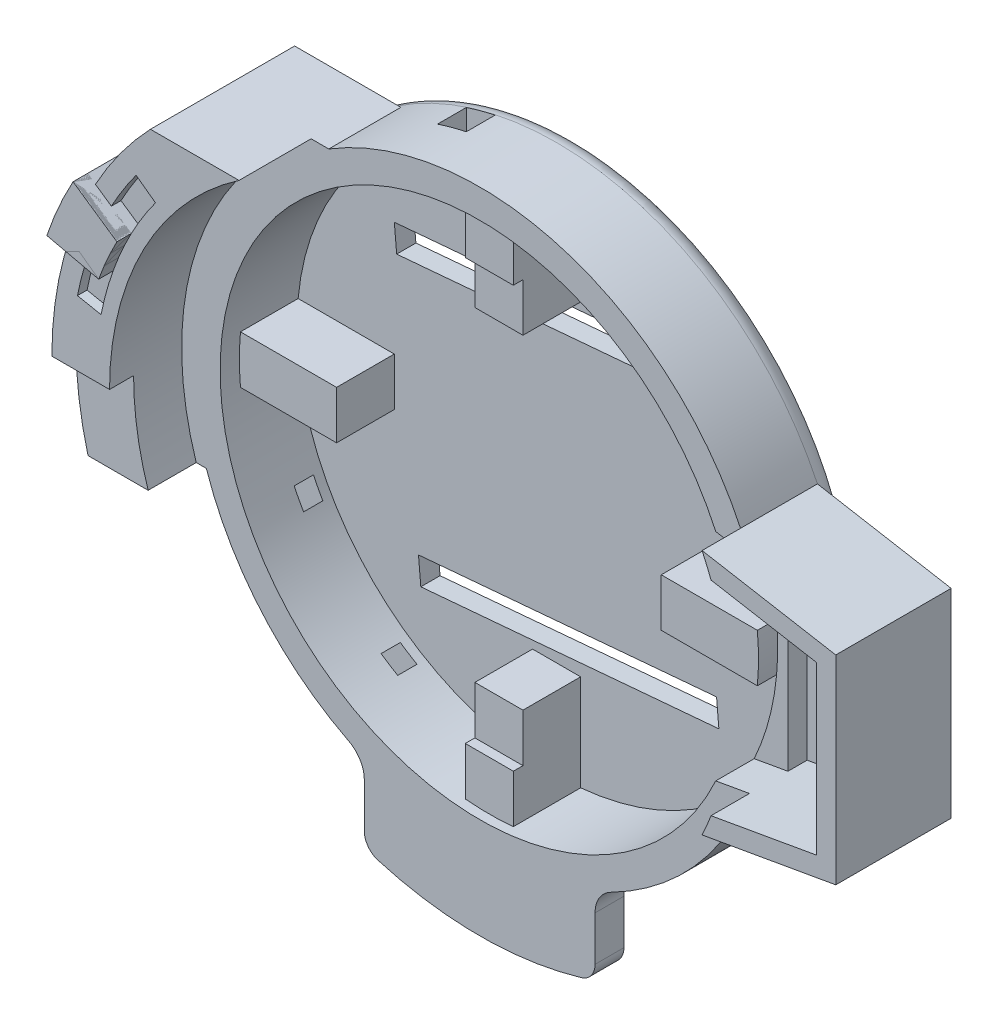
SolidWorks part; units mm, degrees
material "AISI 304"
ref_plane "Front Plane" through (0, 0, 0) normal (0, 0, 1) x (1, 0, 0)
ref_plane "Top Plane" through (0, 0, 0) normal (0, 1, 0) x (1, 0, 0)
ref_plane "Right Plane" through (0, 0, 0) normal (1, 0, 0) x (0, 0, -1)
sketch "草图1" plane through (0, 0, 0) normal (0, 0, 1) x (1, 0, 0)
  circle A0 centre (0, 0) radius 30
  dimension "D1" = 60
extrude "凸台-拉伸1" add sketch "草图1" along normal blind 2
sketch "草图5" plane through (0, 0, 2) normal (0, 0, 1) x (1, 0, 0)
  circle A0 centre (0, 0) radius 30
  circle A1 centre (0, 0) radius 27
  dimension "D1" = 60
  dimension "D2" = 54
extrude "凸台-拉伸2" add sketch "草图5" along normal blind 10 contours A0 | A1
sketch "草图6" plane through (0, 0, 12) normal (0, 0, 1) x (1, 0, 0)
  line L0 (-12, -27.4955) -> (-12, -35.4955)
  line L2 (12, -35.4955) -> (12, -27.4955)
  circle A0 centre (0, 0) radius 30 construction
  arc A1 (-12, -27.4955) -> (12, -27.4955) centre (0, 0) ccw
  arc A2 (-12, -35.4955) -> (12, -35.4955) centre (0, 0) ccw
  dimension "D1" = 8
  dimension "D2" = 24
extrude "凸台-拉伸3" add sketch "草图6" against normal blind 3
fillet "圆角2" radius 3 1 edges at (-12, -27.4955, 10.5)
fillet "圆角3" radius 3 1 edges at (12, -27.4955, 10.5)
sketch "草图8" plane through (0, 0, 12) normal (0, 0, 1) x (1, 0, 0)
  line L0 (27.037, -13) -> (41.037, -13)
  line L1 (41.037, -13) -> (41.037, 13)
  line L2 (41.037, 13) -> (27.037, 13)
  circle A0 centre (0, 0) radius 30 construction
  arc A1 (27.037, -13) -> (27.037, 13) centre (0, 0) ccw
extrude "凸台-拉伸4" add sketch "草图8" against normal blind 6
sketch "草图13" plane through (0, 0, 12) normal (0, 0, 1) x (1, 0, 0)
  line L0 (-26.7466, 25.566) -> (-15.6965, 25.566)
  line L1 (-37, 0) -> (-30, 0)
  arc A0 (-26.7466, 25.566) -> (-37, 0) centre (0, 0) ccw
  arc A1 (-15.6965, 25.566) -> (-30, 0) centre (0, 0) ccw
  dimension "D1" = 37
  dimension "D2" = 30
extrude "凸台-拉伸6" add sketch "草图13" against normal mid plane 15
sketch "草图14" plane through (0, 0, 19.5) normal (0, 0, 1) x (1, 0, 0)
  circle A0 centre (0, 0) radius 31
  dimension "D1" = 62
extrude "切除-拉伸3" cut sketch "草图14" against normal up to surface (7.5 mm away) up to face at (7.2727, -12.6009, 12)
chamfer "倒角4" distance 15 angle 10 1 edges at (41.037, 13, 9) first distance on face at (34.037, 13, 9)
chamfer "倒角5" distance 15 angle 10 1 edges at (41.037, -13, 9) first distance on face at (34.037, -13, 9)
sketch "草图16" plane through (0, 0, 12) normal (0, 0, 1) x (1, 0, 0)
  line L0 (27.9958, 10.6238) -> (39.037, 8.6769)
  line L1 (39.037, 8.6769) -> (39.037, -8.6769)
  line L2 (39.037, -8.6769) -> (21.9943, -11.682)
  line L3 (21.9943, -11.682) -> (18.4523, 12.3065)
  line L4 (18.4523, 12.3065) -> (27.9958, 10.6238)
  line L5 (27.1287, -12.8075) -> (41.037, -10.3551) construction
  line L6 (41.037, -10.3551) -> (41.037, 10.3551) construction
  line L7 (41.037, 10.3551) -> (27.1287, 12.8075) construction
  line L8 (27.1287, -12.8075) -> (41.037, -10.3551)
  line L9 (41.037, -10.3551) -> (41.037, 10.3551)
  line L10 (41.037, 10.3551) -> (27.1287, 12.8075)
  circle M23 centre (0, 0) radius 27
  dimension "D1" = 2
  dimension "D2" = 2
  dimension "D3" = 2
extrude "切除-拉伸6" cut sketch "草图16" against normal blind 4 contours L4 L3 L2 M23 | L4 L2 L1 L0 M23 region at (32.3609, 0, 12) region at (23.1378, 1.239, 12)
sketch "草图17" plane through (0, 0, 12) normal (0, 0, 1) x (1, 0, 0)
  line L0 (-28.4305, -9.5763) -> (-35.7393, -9.5763)
  line L1 (-37, 0) -> (-31, 0) construction
  line L2 (-30, 0) -> (-31, 0) construction
  line L3 (-37, 0) -> (-31, 0)
  line L4 (-30, 0) -> (-31, 0)
  arc A0 (-37, 0) -> (-35.7393, -9.5763) centre (0, 0) ccw
  arc A1 (-30, 0) -> (-28.4305, -9.5763) centre (0, 0) ccw
extrude "凸台-拉伸10" add sketch "草图17" along normal mid plane 10
sketch "草图18" plane through (0, 0, 12) normal (0, 0, 1) x (1, 0, 0)
  line L0 (-35.7393, -9.5763) -> (-28.4305, -9.5763) construction
  line L1 (-30, 0) -> (-31, 0) construction
  line L2 (-35.7393, -9.5763) -> (-28.4305, -9.5763)
  line L3 (-30, 0) -> (-31, 0)
  circle A0 centre (0, 0) radius 31
  circle A1 centre (0, 0) radius 30 construction
  circle A2 centre (0, 0) radius 30
  line M9 (-31, 0) -> (-30, 0)
  arc M10 (-30, 0) -> (-28.4305, -9.5763) centre (0, 0) ccw
extrude "切除-拉伸7" cut sketch "草图18" along normal blind 6 contours A0 L2 M9 M10 region at (-29.984, -4.8293, 12)
sketch "草图19" plane through (0, 0, 2) normal (0, 0, 1) x (1, 0, 0)
  line L0 (-2.5, 26.884) -> (-2.5, 16.884)
  line L1 (-2.5, 16.884) -> (2.5, 16.884)
  line L2 (2.5, 16.884) -> (2.5, 26.884)
  line L3 (26.884, 2.5) -> (16.884, 2.5)
  line L4 (16.884, -2.5) -> (26.884, -2.5)
  line L5 (16.884, 2.5) -> (16.884, -2.5)
  line L6 (2.5, -26.884) -> (2.5, -16.884)
  line L7 (-2.5, -16.884) -> (-2.5, -26.884)
  line L8 (2.5, -16.884) -> (-2.5, -16.884)
  line L9 (-26.884, -2.5) -> (-16.884, -2.5)
  line L10 (-16.884, 2.5) -> (-26.884, 2.5)
  line L11 (-16.884, -2.5) -> (-16.884, 2.5)
  circle A0 centre (0, 0) radius 27 construction
  arc A1 (24.5534, 11.2307) -> (24.5534, -11.2307) centre (0, 0) ccw construction
  arc A2 (2.5, 26.884) -> (-2.5, 26.884) centre (0, 0) ccw
  arc A3 (26.884, -2.5) -> (26.884, 2.5) centre (0, 0) ccw
  arc A4 (-2.5, -26.884) -> (2.5, -26.884) centre (0, 0) ccw
  arc A5 (-26.884, 2.5) -> (-26.884, -2.5) centre (0, 0) ccw
  point P26 (0, 0)
  dimension "D1" = 4
extrude "凸台-拉伸11" add sketch "草图19" along normal blind 8
sketch "草图20" plane through (0, 0, 10) normal (0, 0, 1) x (1, 0, 0)
  line L0 (-2.5, 26.884) -> (-2.5, 21.884)
  line L1 (-2.5, 21.884) -> (2.5, 21.884)
  line L2 (2.5, 21.884) -> (2.5, 26.884)
  line L9 (-2.5, 26.884) -> (-2.5, 16.884)
  line L10 (-2.5, 16.884) -> (2.5, 16.884)
  line L11 (2.5, 16.884) -> (2.5, 26.884)
  line L12 (-2.5, 26.884) -> (-2.5, 21.884)
  line L14 (2.5, 21.884) -> (2.5, 26.884)
  line L17 (2.5, -21.884) -> (2.5, -26.884)
  line L18 (-2.5, -26.884) -> (-2.5, -21.884)
  line L19 (2.5, -21.884) -> (2.5, -26.884)
  line L20 (-2.5, -21.884) -> (2.5, -21.884)
  line L21 (-2.5, -26.884) -> (-2.5, -21.884)
  arc A0 (2.5, -26.884) -> (-2.5, -26.884) centre (0, 0) cw
  arc A3 (2.5, 26.884) -> (-2.5, 26.884) centre (0, 0) ccw
  arc A4 (2.5, 26.884) -> (-2.5, 26.884) centre (0, 0) ccw
  arc M11 (2.5, 26.884) -> (-2.5, 26.884) centre (0, 0) ccw
  line M12 (-2.5, 26.884) -> (-2.5, 16.884)
  line M14 (2.5, 16.884) -> (2.5, 26.884)
  dimension "D1" = 0
extrude "凸台-拉伸12" add sketch "草图20" along normal blind 1 contours A0 L17 L20 L18 | L1 M12 M14 M11 region at (0, 24.4228, 10) region at (0, -24.4228, 10)
sketch "草图21" plane through (0, 0, 19.5) normal (0, 0, 1) x (1, 0, 0)
  line L2 (-28.7344, 15.1849) -> (-33.2959, 18.3135)
  line L3 (-30.6288, 10.8687) -> (-36.0194, 12.1079)
  arc A0 (-33.2959, 18.3135) -> (-36.0194, 12.1079) centre (0, 0) ccw
  arc A1 (-28.7344, 15.1849) -> (-30.6288, 10.8687) centre (0, 0) ccw
extrude "凸台-拉伸13" add sketch "草图21" along normal blind 1.5
sketch "草图26" plane through (0, 0, 21) normal (0, 0, 1) x (1, 0, 0)
  line L2 (-28.7344, 15.1849) -> (-33.2959, 18.3135)
  line L3 (-36.0194, 12.1079) -> (-30.6288, 10.8687)
  line L4 (-28.7344, 15.1849) -> (-33.2959, 18.3135)
  line L5 (-36.0194, 12.1079) -> (-30.6288, 10.8687)
  arc A2 (-28.7344, 15.1849) -> (-30.6288, 10.8687) centre (0, 0) ccw
  arc A3 (-33.2959, 18.3135) -> (-36.0194, 12.1079) centre (0, 0) ccw
  arc A4 (-28.7344, 15.1849) -> (-30.6288, 10.8687) centre (0, 0) ccw
  arc A5 (-33.2959, 18.3135) -> (-36.0194, 12.1079) centre (0, 0) ccw
  dimension "D1" = 0
extrude "凸台-拉伸14" add sketch "草图26" against normal up to surface (16.5 mm away) separate body contours A4 L5 A5 L4 up to face at (-28.8109, 13.4966, 4.5)
sketch "草图28" plane through (0, 0, 19.5) normal (0, 0, 1) x (1, 0, 0)
  line L1 (-26.2215, 19.2011) -> (-28.2386, 20.6781)
  line L2 (-31.8835, 6.3003) -> (-34.3361, 6.7849)
  line L3 (-35.04, 11.8827) -> (-30.6288, 10.8687) construction
  line L4 (-35.04, 11.8827) -> (-30.6288, 10.8687)
  line L5 (-28.7344, 15.1849) -> (-32.4671, 17.7451) construction
  line L6 (-28.7344, 15.1849) -> (-32.4671, 17.7451)
  arc A0 (-30.6288, 10.8687) -> (-31.8835, 6.3003) centre (0, 0) ccw
  arc A1 (-33.0803, 11.4322) -> (-34.3361, 6.7849) centre (0, 0) ccw
  arc A3 (-26.2215, 19.2011) -> (-28.7344, 15.1849) centre (0, 0) ccw
  arc A4 (-28.2386, 20.6781) -> (-30.8088, 16.6077) centre (0, 0) ccw
  line M5 (-30.6288, 10.8687) -> (-35.04, 11.8827)
extrude "切除-拉伸8" cut sketch "草图28" against normal blind 1 contours A1 L2 A0 M5 | L1 A4 L6 A3 region at (-28.5514, 17.9499, 19.5) region at (-32.5399, 8.8621, 19.5)
sketch "草图31" plane through (0, 0, 6) normal (0, 0, -1) x (-1, 0, 0)
  line L3 (-41.037, 10.3551) -> (-41.037, -10.3551)
  line L4 (-41.037, -10.3551) -> (-27.1287, -12.8075)
  line L5 (-27.1287, 12.8075) -> (-41.037, 10.3551)
  line L6 (-41.037, 10.3551) -> (-41.037, -10.3551)
  line L7 (-41.037, -10.3551) -> (-27.1287, -12.8075)
  line L8 (-27.1287, 12.8075) -> (-41.037, 10.3551)
  arc A1 (-27.1287, 12.8075) -> (-27.1287, -12.8075) centre (0, 0) ccw
  arc A2 (-27.1287, 12.8075) -> (-27.1287, -12.8075) centre (0, 0) ccw
  dimension "D1" = 0
extrude "凸台-拉伸15" add sketch "草图31" along normal blind 2
sketch "草图32" plane through (0, 0, 8) normal (0, 0, 1) x (1, 0, 0)
  line L0 (39.037, -8.6769) -> (24.5534, -11.2307) construction
  line L1 (39.037, 8.6769) -> (39.037, -8.6769) construction
  line L2 (24.5534, 11.2307) -> (39.037, 8.6769) construction
  line L3 (39.037, -8.6769) -> (28.0602, -10.6124)
  line L4 (39.037, 8.6769) -> (39.037, -8.6769)
  line L5 (28.0602, 10.6124) -> (39.037, 8.6769)
  line L6 (28.0602, 10.6124) -> (28.0602, -10.6124)
  circle A0 centre (0, 0) radius 30 construction
extrude "切除-拉伸9" cut sketch "草图32" against normal blind 2
sketch "草图33" plane through (0, 0, 0) normal (0, 0, -1) x (-1, 0, 0)
  circle A0 centre (0, 0) radius 30
extrude "切除-拉伸10" cut sketch "草图33" against normal blind 2
sketch "草图34" plane through (0, 0, 2) normal (0, 0, -1) x (-1, 0, 0)
  circle A0 centre (0, 0) radius 30
extrude "凸台-拉伸16" add sketch "草图34" against normal blind 2
fillet "圆角4" radius 2 1 edges at (-12, -35.4955, 10.5)
fillet "圆角5" radius 2 1 edges at (12, -35.4955, 10.5)
sketch "草图35" plane through (0, 0, 4) normal (0, 0, 1) x (1, 0, 0)
  line L0 (0, 30) -> (0, -27) construction
  line L1 (-16.8773, 14.3757) -> (14.1246, 17.088)
  line L2 (-16.8773, 14.3757) -> (-16.6365, 11.6234)
  line L3 (-16.6365, 11.6234) -> (14.3654, 14.3357)
  line L4 (14.1246, 17.088) -> (14.3654, 14.3357)
  line L5 (-16.884, 0) -> (16.884, 0) construction
  line L6 (0, 0) -> (41.8509, 3.6615) construction
  line L7 (16.8773, -14.3757) -> (16.6365, -11.6234)
  line L8 (-14.3654, -14.3357) -> (16.6365, -11.6234)
  line L9 (-14.1246, -17.088) -> (-14.3654, -14.3357)
  line L10 (-14.1246, -17.088) -> (16.8773, -14.3757)
  dimension "D1" = 5
extrude "切除-拉伸11" cut sketch "草图35" against normal blind 10
fillet "圆角6" radius 2 1 edges at (-30, 0, 2)
ref_plane "基准面1" through (7.192, 7.192, 0) normal (-0.7071, -0.7071, 0) x (0, 0, 1)
sketch "草图37" plane through (7.192, 7.192, 0) normal (-0.7071, -0.7071, 0) x (0, 0, 1)
  line L1 (4.9344, 8.986) -> (6.9344, 8.986)
  line L2 (4.9344, 8.986) -> (4.9344, 6.986)
  line L3 (4.9344, 6.986) -> (6.9344, 6.986)
  line L4 (6.9344, 8.986) -> (6.9344, 6.986)
  line L5 (4.9344, -4.8884) -> (6.9344, -4.8884)
  line L6 (4.9344, -4.8884) -> (4.9344, -6.8884)
  line L7 (4.9344, -6.8884) -> (6.9344, -6.8884)
  line L8 (6.9344, -4.8884) -> (6.9344, -6.8884)
extrude "切除-拉伸12" cut sketch "草图37" along normal blind 65 contours L2 L1 L4 L3 | L6 L5 L8 L7
ref_plane "基准面2" through (-21.9406, -20.46, 0) normal (-0.7314, -0.682, 0) x (0, 0, -1)
sketch "草图38" plane through (0, 0, 0) normal (0, 1, 0) x (1, 0, 0)
  line L7 (-9.3371, -7.0519) -> (-9.3371, -4.0519)
  line L8 (-6.3371, -4.0519) -> (-9.3371, -4.0519)
  line L9 (-6.3371, -7.0519) -> (-6.3371, -4.0519)
  line L10 (-6.3371, -7.0519) -> (-9.3371, -7.0519)
extrude "切除-拉伸14" cut sketch "草图38" along normal blind 45
ref_plane "基准面3" through (-7.192, 7.192, 0) normal (0.7071, -0.7071, 0) x (-0.7071, -0.7071, 0)
ref_plane "基准面4" through (-0.1209, 0.1209, 0) normal (0.7071, -0.7071, 0) x (-0.7071, -0.7071, 0)
sketch "草图40" plane through (0, 0, 12) normal (0, 0, 1) x (1, 0, 0)
  line L0 (27.1287, -12.8075) -> (41.037, -10.3551) construction
  line L1 (28.0602, -10.6124) -> (39.037, -8.6769) construction
  line L2 (39.037, 8.6769) -> (39.037, -8.6769) construction
  line L3 (41.037, -10.3551) -> (41.037, 10.3551) construction
  line L4 (39.037, 8.6769) -> (28.0602, 10.6124) construction
  line L5 (41.037, 10.3551) -> (27.1287, 12.8075) construction
  line L6 (27.1287, -12.8075) -> (41.037, -10.3551)
  line L7 (28.0602, -10.6124) -> (39.037, -8.6769)
  line L8 (39.037, 8.6769) -> (39.037, -8.6769)
  line L9 (41.037, -10.3551) -> (41.037, 10.3551)
  line L10 (39.037, 8.6769) -> (28.0602, 10.6124)
  line L11 (41.037, 10.3551) -> (27.1287, 12.8075)
  arc A0 (27.1287, -12.8075) -> (28.0602, -10.6124) centre (0, 0) ccw
  arc A1 (28.0602, 10.6124) -> (27.1287, 12.8075) centre (0, 0) ccw
extrude "凸台-拉伸17" add sketch "草图40" along normal blind 4
